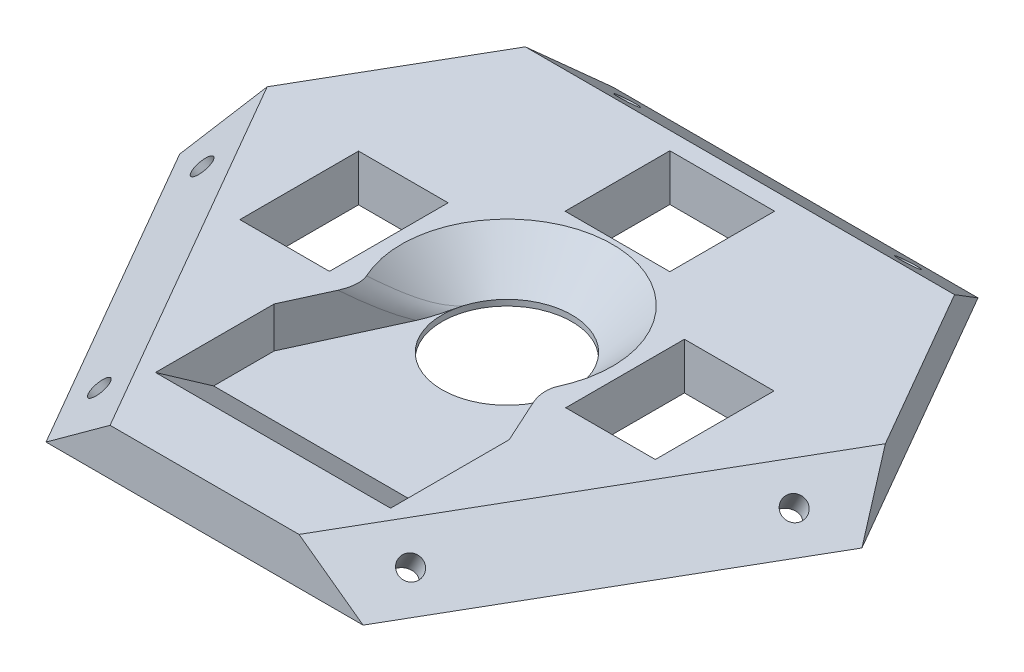
SolidWorks part; units mm, degrees
ref_plane "Front Plane" through (0, 0, 0) normal (0, 0, 1) x (1, 0, 0)
ref_plane "Top Plane" through (0, 0, 0) normal (0, 1, 0) x (1, 0, 0)
ref_plane "Right Plane" through (0, 0, 0) normal (1, 0, 0) x (0, 0, -1)
sketch "Sketch1" plane through (0, 0, 0) normal (0, 1, 0) x (1, 0, 0)
  line L7 (-60, 0) -> (-30, -51.9615)
  line L8 (-30, -51.9615) -> (30, -51.9615)
  line L9 (30, -51.9615) -> (60, 0)
  line L10 (60, 0) -> (30, 51.9615)
  line L11 (30, 51.9615) -> (-30, 51.9615)
  line L12 (-30, 51.9615) -> (-60, 0)
  circle A1 centre (0, 0) radius 51.9615 construction
  dimension "D1" = 60
extrude "Boss-Extrude1" add sketch "Sketch1" along normal blind 8
chamfer "Chamfer1" distance 10 angle 50 3 edges at (0, 8, -51.9615) (-45, 8, 25.9808) (45, 8, 25.9808) first distance on face at (0, 4, -51.9615) first distance on face at (-45, 4, 25.9808) first distance on face at (45, 4, 25.9808)
sketch "Sketch4" plane through (17.74, 24.4124, 10.2422) normal (0.5567, 0.766, 0.3214) x (0.8301, -0.4979, -0.251)
  line L0 (46.1828, 6.3514) -> (3.0135, -46.52) construction
  line L1 (43.1032, 12.419) -> (49.2624, 0.2838) construction
  line L2 (9.5744, -48.3238) -> (-3.5474, -44.7162) construction
  circle A0 centre (39.8583, -1.3946) radius 1.85
  circle A1 centre (9.338, -38.774) radius 1.85
  dimension "D1" = 3.7
  dimension "D2" = 10
  dimension "D3" = 10
extrude "Cut-Extrude1" cut sketch "Sketch4" against normal through all
sketch "Sketch5" plane through (0, 0, 0) normal (0, 1, 0) x (1, 0, 0)
  circle A0 centre (0, 0) radius 11.15
  dimension "D1" = 22.3
extrude "Cut-Extrude3" cut sketch "Sketch5" along normal through all
sketch "Sketch6" plane through (-17.74, 24.4124, 10.2422) normal (-0.5567, 0.766, 0.3214) x (0.8307, 0.5133, 0.2154)
  line L0 (-45.9011, 8.1412) -> (-4.8189, -46.3678) construction
  line L1 (-49.2141, 2.1979) -> (-42.5881, 14.0846) construction
  line L2 (1.8071, -44.8203) -> (-11.445, -47.9153) construction
  circle A0 centre (-39.8823, 0.1553) radius 1.85
  circle A1 centre (-10.8377, -38.3819) radius 1.85
  dimension "D1" = 3.7
  dimension "D2" = 10
  dimension "D3" = 10
extrude "Cut-Extrude4" cut sketch "Sketch6" against normal through all
sketch "Sketch7" plane through (0, 24.4124, -20.4844) normal (0, 0.766, -0.6428) x (1, 0, 0)
  line L0 (34.1284, 31.7561) -> (-34.1284, 31.7561) construction
  line L1 (31.3761, 37.979) -> (36.8806, 25.5332) construction
  line L2 (-36.8806, 25.5332) -> (-31.3761, 37.979) construction
  circle A0 centre (-24.1284, 31.7561) radius 1.85
  circle A1 centre (24.1284, 31.7561) radius 1.85
  dimension "D1" = 3.7
  dimension "D2" = 10
  dimension "D3" = 10
extrude "Cut-Extrude5" cut sketch "Sketch7" against normal through all
sketch "Sketch8" plane through (0, 8, 0) normal (0, 1, 0) x (1, 0, 0)
  line L0 (-35.7, -10.2) -> (-35.7, 10.2)
  line L1 (-35.5, -10) -> (-20.5, -10) construction
  line L2 (-35.5, -10) -> (-35.5, 10) construction
  line L3 (-35.5, 10) -> (-20.5, 10) construction
  line L4 (-20.5, -10) -> (-20.5, 10) construction
  line L5 (-35.5, -10) -> (-20.5, 10) construction
  line L6 (-35.5, 10) -> (-20.5, -10) construction
  line L7 (20.5, -10) -> (35.5, -10) construction
  line L8 (20.5, -10) -> (20.5, 10) construction
  line L9 (20.5, 10) -> (35.5, 10) construction
  line L10 (35.5, -10) -> (35.5, 10) construction
  line L11 (20.5, -10) -> (35.5, 10) construction
  line L12 (20.5, 10) -> (35.5, -10) construction
  line L13 (-35.7, 10.2) -> (-20.3, 10.2)
  line L14 (-20.3, -10.2) -> (-20.3, 10.2)
  line L15 (-35.7, -10.2) -> (-20.3, -10.2)
  line L16 (20.3, -10.2) -> (20.3, 10.2)
  line L17 (20.3, 10.2) -> (35.7, 10.2)
  line L18 (35.7, -10.2) -> (35.7, 10.2)
  line L19 (20.3, -10.2) -> (35.7, -10.2)
  point P0 (-28, 0)
  point P3 (0, 0)
  point P4 (0, 0)
  point P10 (28, 0)
  dimension "D1" = 20
  dimension "D2" = 15
  dimension "D3" = 28
  dimension "D4" = 15
  dimension "D5" = 20
  dimension "D6" = 28
  dimension "D7" = 0.2
  dimension "D8" = 0.2
extrude "Cut-Extrude6" cut sketch "Sketch8" against normal through all
sketch "Sketch9" plane through (0, 8, 0) normal (0, 1, 0) x (1, 0, 0)
  line L0 (-20.2, -30.2) -> (-20.2, -19.8)
  line L1 (-20, -30) -> (20, -30) construction
  line L2 (-20, -30) -> (-20, -20) construction
  line L3 (-20, -20) -> (20, -20) construction
  line L4 (20, -30) -> (20, -20) construction
  line L5 (-20, -30) -> (20, -20) construction
  line L6 (-20, -20) -> (20, -30) construction
  line L7 (-20.2, -19.8) -> (20.2, -19.8)
  line L8 (20.2, -30.2) -> (20.2, -19.8)
  line L9 (-20.2, -30.2) -> (20.2, -30.2)
  point P0 (0, -25)
  dimension "D1" = 10
  dimension "D2" = 40
  dimension "D3" = 20
  dimension "D4" = 0.2
extrude "Cut-Extrude7" cut sketch "Sketch9" against normal offset from surface (7 mm away) 1 up to face at (-28, 0, 0)
sketch "Sketch10" plane through (0, 8, 0) normal (0, 1, 0) x (1, 0, 0)
  line L0 (-20.2, -19.8) -> (-11.15, 0)
  line L1 (-11.15, 0) -> (11.15, 0)
  line L2 (11.15, 0) -> (20.2, -19.8)
  line L3 (20.2, -19.8) -> (-20.2, -19.8)
  circle A0 centre (0, 0) radius 11.15 construction
extrude "Cut-Extrude8" cut sketch "Sketch10" against normal up to surface (7 mm away) up to face at (0, 1, 25)
chamfer "Chamfer2" distance 7 angle 45 1 edges at (0, 8, -11.15)
chamfer "Chamfer3" distance 10 angle 35 1 edges at (0, 8, 30.2) first distance on face at (0, 8, 15.2208)
fillet "Fillet1" radius 3 2 edges
sketch "Sketch11" plane through (0, 8, 0) normal (0, 1, 0) x (1, 0, 0)
  line L1 (-9, 19) -> (9, 19)
  line L2 (-9, 19) -> (-9, 37)
  line L3 (-9, 37) -> (9, 37)
  line L4 (9, 19) -> (9, 37)
  line L5 (-9, 19) -> (9, 37) construction
  line L6 (-9, 37) -> (9, 19) construction
  point P0 (0, 28)
  dimension "D1" = 18
  dimension "D2" = 18
  dimension "D3" = 28
extrude "Cut-Extrude9" cut sketch "Sketch11" against normal through all
equation "\"`9\"=8"
